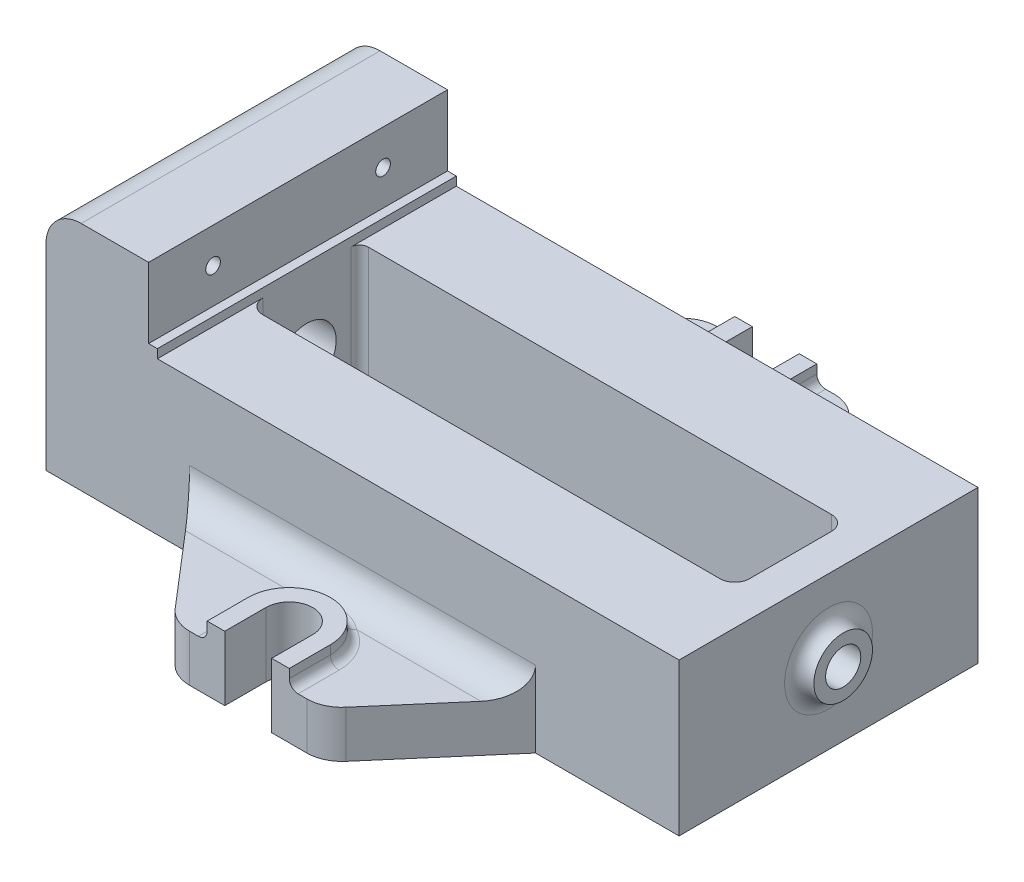
SolidWorks part; units mm, degrees
ref_plane "Front Plane" through (0, 0, 0) normal (0, 0, 1) x (1, 0, 0)
ref_plane "Top Plane" through (0, 0, 0) normal (0, 1, 0) x (1, 0, 0)
ref_plane "Right Plane" through (0, 0, 0) normal (1, 0, 0) x (0, 0, -1)
sketch "Sketch1" plane through (0, 0, 0) normal (0, 1, 0) x (1, 0, 0)
  line L1 (-108, -51) -> (108, -51)
  line L2 (-108, -51) -> (-108, 51)
  line L3 (-108, 51) -> (108, 51)
  line L4 (108, -51) -> (108, 51)
  line L5 (-108, -51) -> (108, 51) construction
  line L6 (-108, 51) -> (108, -51) construction
  point P0 (0, 0)
  dimension "D1" = 216
  dimension "D2" = 102
extrude "Extrude1" add sketch "Sketch1" along normal blind 79
sketch "Sketch2" plane through (0, 0, 51) normal (0, 0, 1) x (1, 0, 0)
  line L0 (-73, 79) -> (-73, 55)
  line L1 (-108, 79) -> (108, 79) construction
  line L2 (-73, 55) -> (-70, 55)
  line L3 (-70, 55) -> (-70, 52)
  line L4 (-70, 52) -> (108, 52)
  line L5 (108, 79) -> (108, 0) construction
  line L6 (-73, 79) -> (108, 79)
  line L7 (108, 79) -> (108, 52)
  dimension "D1" = 35
  dimension "D2" = 3
  dimension "D3" = 27
  dimension "D4" = 3
extrude "Extrude2" cut sketch "Sketch2" against normal through all
fillet "Fillet1" radius 12 1 edges at (-108, 79, 0)
sketch "Sketch3" plane through (0, 52, 0) normal (0, 1, 0) x (1, 0, 0)
  line L0 (108, 51) -> (108, -51) construction
  line L1 (-65, -20) -> (91, -20)
  line L2 (-70, 15) -> (-70, -15)
  line L3 (-67, 18) -> (91, 18)
  line L4 (96, -15) -> (96, 13)
  line L5 (-70, 0) -> (-51.1928, 0) construction
  line L6 (-70, -51) -> (108, -51) construction
  line L7 (-70, 51) -> (-70, -51) construction
  line L8 (-70, 51) -> (-70, -51) construction
  arc A0 (-67, 18) -> (-70, 15) centre (-67, 15) ccw
  arc A1 (-65, -20) -> (-70, -15) centre (-65, -15) cw
  arc A2 (96, -15) -> (91, -20) centre (91, -15) cw
  arc A3 (96, 13) -> (91, 18) centre (91, 13) ccw
  point P0 (0, 0)
  point P14 (-70, 18)
  point P17 (-70, -20)
  point P20 (96, -20)
  point P23 (96, 18)
  dimension "D3" = 3
  dimension "D4" = 5
  dimension "D1" = 12
  dimension "D2" = 38
  dimension "D5" = 51
extrude "Extrude3" cut sketch "Sketch3" against normal through all
sketch "Sketch4" plane through (0, 0, 0) normal (0, 1, 0) x (1, 0, 0)
  line L0 (0, 76) -> (0, -55.6444) construction
  line L1 (-8, 90) -> (-20, 90)
  line L2 (-29.1043, 85.8174) -> (-59, 51)
  line L3 (-70, 51) -> (108, 51) construction
  line L4 (8, 90) -> (20, 90)
  line L5 (29.1043, 85.8174) -> (59, 51)
  line L6 (-8, 90) -> (-8, 76)
  line L7 (8, 90) -> (8, 76)
  line L8 (-153.0146, 0) -> (215.8218, 0) construction
  line L9 (8, -90) -> (8, -76)
  line L10 (-8, -90) -> (-8, -76)
  line L11 (29.1043, -85.8174) -> (59, -51)
  line L12 (8, -90) -> (20, -90)
  line L13 (-29.1043, -85.8174) -> (-59, -51)
  line L14 (-8, -90) -> (-20, -90)
  line L15 (-59, 51) -> (59, 51)
  line L16 (59, -51) -> (-59, -51)
  arc A0 (-8, 76) -> (8, 76) centre (0, 76) ccw
  arc A1 (29.1043, 85.8174) -> (20, 90) centre (20, 78) ccw
  arc A2 (-20, 90) -> (-29.1043, 85.8174) centre (-20, 78) ccw
  arc A3 (-20, -90) -> (-29.1043, -85.8174) centre (-20, -78) cw
  arc A4 (29.1043, -85.8174) -> (20, -90) centre (20, -78) cw
  arc A5 (-8, -76) -> (8, -76) centre (0, -76) cw
  point P3 (-108, 51)
  point P18 (25.5129, 90)
  point P21 (-25.5129, 90)
  point P37 (-25.5129, -90)
  point P38 (25.5129, -90)
  dimension "D1" = 8
  dimension "D3" = 12
  dimension "D4" = 12
  dimension "D10" = 8
  dimension "D2" = 90
  dimension "D5" = 40
  dimension "D6" = 39
  dimension "D7" = 39
  dimension "D8" = 14
  dimension "D9" = 14
extrude "Extrude4" add sketch "Sketch4" along normal blind 16
sketch "Sketch5" plane through (0, 16, 0) normal (0, 1, 0) x (1, 0, 0)
  line L0 (-14, -90) -> (-14, -76)
  line L1 (-20, -90) -> (-8, -90) construction
  line L2 (14, -90) -> (14, -76)
  line L3 (8, -90) -> (20, -90) construction
  line L5 (14, 90) -> (14, 76)
  line L6 (-14, 90) -> (-14, 76)
  line L7 (-14, 90) -> (-8, 90)
  line L8 (8, 90) -> (14, 90)
  line L9 (-8, 90) -> (-8, 76)
  line L10 (8, 90) -> (8, 76)
  line L11 (-8, -90) -> (-8, -76)
  line L12 (8, -90) -> (8, -76)
  line L13 (8, -90) -> (14, -90)
  line L14 (-14, -90) -> (-8, -90)
  arc A0 (-14, -76) -> (14, -76) centre (0, -76) cw
  arc A1 (-14, 76) -> (14, 76) centre (0, 76) ccw
  arc A2 (-8, 76) -> (8, 76) centre (0, 76) ccw
  arc A3 (-8, -76) -> (8, -76) centre (0, -76) cw
  dimension "D1" = 14
  dimension "D2" = 14
extrude "Extrude5" add sketch "Sketch5" along normal blind 6
fillet "Fillet3" radius 10 1 edges at (0, 16, 51)
fillet "Fillet4" radius 3 3 edges at (-14, 16, 83) (14, 16, 83) (0, 16, 62)
fillet "Fillet5" radius 10 1 edges at (0, 16, -51)
fillet "Fillet6" radius 3 3 edges at (14, 16, -83) (0, 16, -62) (-14, 16, -83)
sketch "Sketch6" plane through (-73, 0, 0) normal (1, 0, 0) x (0, 0, -1)
  point P5 (-29, 67)
  point P6 (29, 67)
  dimension "D1" = 58
hole_wizard "M6 Tapped Hole1" positions "3DSketch3" profile "Sketch11" tap size "M6" standard "ISO"
sketch3d "3DSketch3"
  point P0 (-73, 67, 29)
  point P3 (-73, 67, -29)
sketch "Sketch11" plane through (-73, 67, 29) normal (0, 1, 0) x (0, 0, -1)
  line L0 (0, 0) -> (0, 15.5022)
  line L1 (0, 15.5022) -> (2.5, 14)
  line L2 (2.5, 14) -> (2.5, 0)
  line L5 (2.5, 0) -> (0, 0)
  line L10 (0, 15.5022) -> (-2.5, 14) construction
  line L11 (0, -6.35) -> (0, 107.95) construction
  dimension "Tap Drill Dia." = 5
  dimension "Tap Drill Depth" = 14
  dimension "Drill Angle" = 118
cosmetic thread "Hole Thread1" parameters "D1"=12, "D2"=6
cosmetic thread "Hole Thread2" parameters "D1"=12, "D2"=6
sketch "Sketch13" plane through (108, 0, 0) normal (1, 0, 0) x (0, 0, -1)
  line L0 (0, 0) -> (0, 91.2921) construction
  circle A0 centre (0, 27) radius 10
  circle A1 centre (0, 27) radius 6
  dimension "D1" = 20
  dimension "D2" = 27
extrude "Extrude7" add sketch "Sketch13" along normal blind 5
sketch "Sketch14" plane through (108, 0, 0) normal (1, 0, 0) x (0, 0, -1)
  circle A0 centre (0, 27) radius 6
  dimension "D1" = 12
extrude "Extrude8" cut sketch "Sketch14" against normal up to next
fillet "Fillet7" radius 5 1 edges at (108, 27, 10)
sketch "Sketch15" plane through (-108, 0, 0) normal (-1, 0, 0) x (0, 0, 1)
  line L0 (0, 92.4335) -> (0, -8.2971) construction
  circle A0 centre (0, 27) radius 16
  dimension "D2" = 32
  dimension "D1" = 27
extrude "Extrude9" add sketch "Sketch15" along normal blind 5
sketch "Sketch16" plane through (-113, 0, 0) normal (-1, 0, 0) x (0, 0, 1)
  circle A0 centre (0, 27) radius 10
  dimension "D1" = 20
extrude "Extrude10" cut sketch "Sketch16" against normal up to next
sketch "Sketch17" plane through (0, 0, 0) normal (0, -1, 0) x (1, 0, 0)
  line L0 (108, 51) -> (108, -51) construction
  line L1 (-64, -28) -> (90, -28)
  line L2 (-70, -22) -> (-70, 22)
  line L3 (-64, 28) -> (90, 28)
  line L4 (96, -22) -> (96, 22)
  arc A0 (-70, 22) -> (-64, 28) centre (-64, 22) cw
  arc A1 (-64, -28) -> (-70, -22) centre (-64, -22) cw
  arc A2 (90, 28) -> (96, 22) centre (90, 22) cw
  arc A3 (90, -28) -> (96, -22) centre (90, -22) ccw
  point P13 (-70, 28)
  point P16 (-70, -28)
  dimension "D4" = 6
  dimension "D5" = 6
  dimension "D1" = 12
  dimension "D2" = 56
extrude "Extrude11" cut sketch "Sketch17" against normal blind 12
